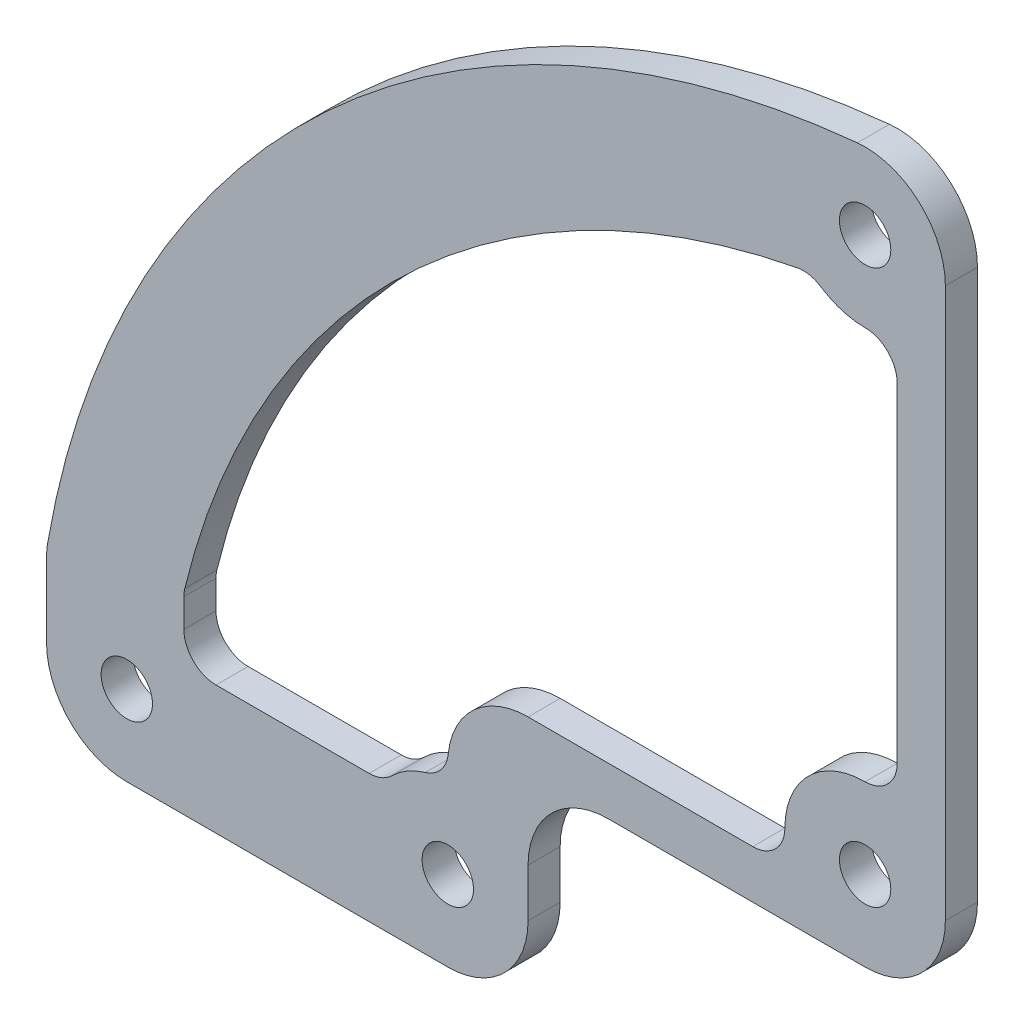
SolidWorks part; units mm, degrees
material "6061 合金"
ref_plane "正面" through (0, 0, 0) normal (0, 0, 1) x (1, 0, 0)
ref_plane "平面" through (0, 0, 0) normal (0, 1, 0) x (1, 0, 0)
ref_plane "右側面" through (0, 0, 0) normal (1, 0, 0) x (0, 0, -1)
sketch "ｽｹｯﾁ1" plane through (0, 0, 0) normal (0, 0, 1) x (1, 0, 0)
  line L4 (-30, 10) -> (-30, 0)
  line L5 (-30, 0) -> (0, 0)
  line L6 (0, 0) -> (0, 13)
  line L7 (0, 13) -> (26, 13)
  line L8 (26, 13) -> (26, 57.5)
  line L9 (-30, 5) -> (0, 5) construction
  line L10 (21, 57.2793) -> (21, 13) construction
  line L12 (-5, 11) -> (-5, 10)
  line L13 (0, 16) -> (16, 16)
  line L14 (16, 16) -> (16, 18)
  line L16 (21, 23) -> (23, 23)
  line L17 (23, 23) -> (23, 47.5)
  line L18 (23, 47.5) -> (21, 47.5)
  line L20 (-9, 8) -> (-21.4425, 8)
  line L21 (-21.4425, 8) -> (-21.4425, 12)
  arc A1 (26, 57.5) -> (-30, 10) centre (26, 0.7395) ccw
  circle A2 centre (-25, 5) radius 1.6
  circle A3 centre (-5, 5) radius 1.6
  circle A4 centre (21, 18) radius 1.6
  circle A5 centre (21, 52.5) radius 1.6
  arc A7 (16, 18) -> (21, 23) centre (21, 18) cw
  arc A8 (21, 47.5) -> (17.6579, 48.7811) centre (21, 52.5) cw
  arc A10 (-21.4425, 12) -> (17.6579, 48.7811) centre (26, 0.7395) cw
  arc A11 (0, 16) -> (-5, 11) centre (0, 11) ccw
  arc A12 (-9, 8) -> (-5, 10) centre (-5, 5) cw
  point P9 (-21.2822, 13)
  point P33 (-4.3452, 10)
  point P36 (0, 0)
  dimension "D7" = 20
  dimension "D8" = 3.2
  dimension "D10" = 5
  dimension "D12" = 5
  dimension "D13" = 4
  dimension "D14" = 16
  dimension "D18" = 8
  dimension "D19" = 5
  dimension "D20" = 10
  dimension "D1" = 30
  dimension "D2" = 56
  dimension "D3" = 57.5
  dimension "D4" = 13
  dimension "D5" = 5
  dimension "D6" = 5
  dimension "D9" = 51
  dimension "D11" = 39.5
  dimension "D15" = 5
  dimension "D16" = 2
  dimension "D17" = 3
  dimension "D21" = 3
  dimension "D22" = 5
extrude "ﾎﾞｽ - 押し出し1" add sketch "ｽｹｯﾁ1" along normal blind 2
fillet "ﾌｨﾚｯﾄ1" radius 5 6 edges at (26, 57.5, 1) (26, 13, 1) (0, 13, 1) (0, 0, 1) (-30, 0, 1) (-30, 10, 1)
fillet "ﾌｨﾚｯﾄ2" radius 2 8 edges at (17.6579, 48.7811, 1) (23, 47.5, 1) (16, 16, 1) (23, 23, 1) (-5, 10, 1) (-9, 8, 1) (-21.4425, 8, 1) (-21.4425, 12, 1)
